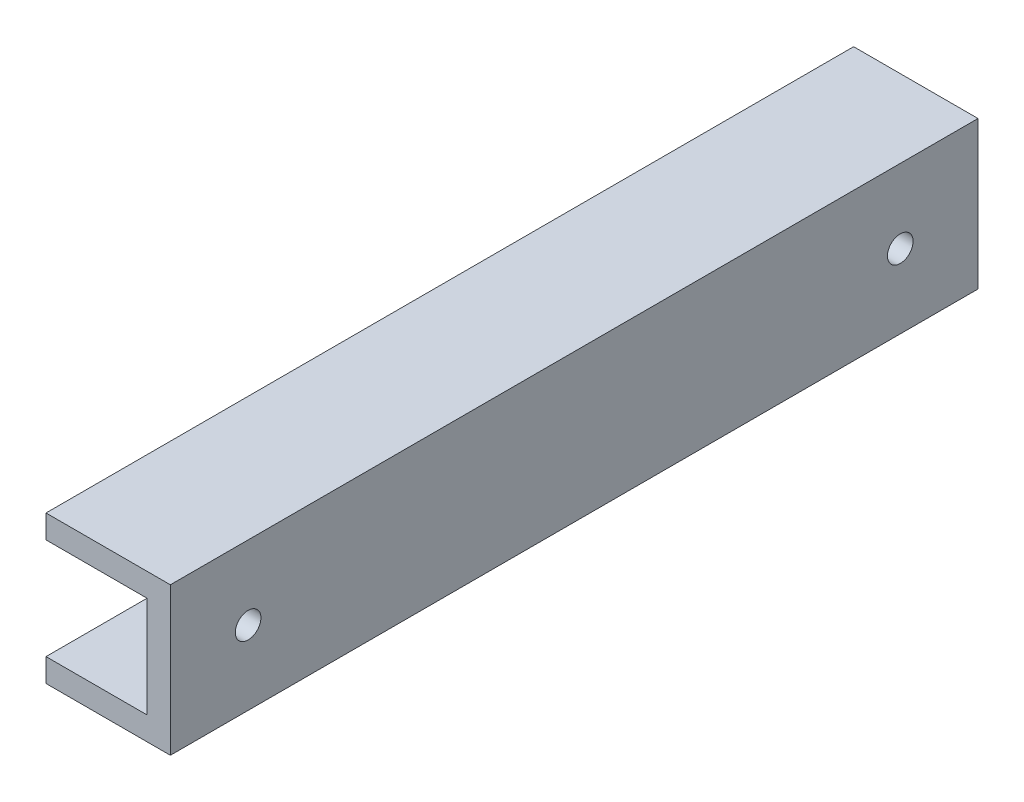
SolidWorks part; units mm, degrees
ref_plane "前视基准面" through (0, 0, 0) normal (0, 0, 1) x (1, 0, 0)
ref_plane "上视基准面" through (0, 0, 0) normal (0, 1, 0) x (1, 0, 0)
ref_plane "右视基准面" through (0, 0, 0) normal (1, 0, 0) x (0, 0, -1)
sketch "草图1" plane through (0, 0, 0) normal (0, 0, 1) x (1, 0, 0)
  line L1 (0, 0) -> (13, 0)
  line L2 (0, 0) -> (0, 13)
  line L3 (0, 13) -> (13, 13)
  line L4 (13, 0) -> (13, 13)
  dimension "D1" = 13
  dimension "D2" = 13
extrude "拉伸-薄壁1" add sketch "草图1" along normal blind 103.9 thin thin type one direction wall 3
sketch "草图2" plane through (-3, 0, 0) normal (-1, 0, 0) x (0, 0, 1)
  line L0 (0, 16) -> (0, -3) construction
  line L1 (103.9, 16) -> (103.9, -3) construction
  circle A0 centre (10, 6.5) radius 1.65
  circle A1 centre (93.9, 6.5) radius 1.65
  dimension "D1" = 3.3
  dimension "D2" = 3.3
  dimension "D3" = 10
  dimension "D4" = 10
extrude "切除-拉伸1" cut sketch "草图2" against normal blind 30
sketch "草图3" plane through (-3, 0, 0) normal (-1, 0, 0) x (0, 0, 1)
  line L1 (-5.2954, 23.3125) -> (111.6198, 23.3125)
  line L2 (-5.2954, 23.3125) -> (-5.2954, -22.907)
  line L3 (-5.2954, -22.907) -> (111.6198, -22.907)
  line L4 (111.6198, 23.3125) -> (111.6198, -22.907)
extrude "切除-拉伸2" cut sketch "草图3" against normal blind 3
sketch "草图4" plane through (13, 0, 0) normal (-1, 0, 0) x (0, 0, 1)
  line L0 (103.9, 13) -> (0, 13) construction
  line L1 (23, 13) -> (28, 13)
  line L2 (23, 13) -> (23, 0)
  line L3 (23, 0) -> (28, 0)
  line L4 (28, 13) -> (28, 0)
  line L5 (103.9, 0) -> (0, 0) construction
  line L6 (103.9, 13) -> (0, 13) construction
  line L7 (75.9, 13) -> (80.9, 13)
  line L8 (75.9, 13) -> (75.9, 0)
  line L9 (75.9, 0) -> (80.9, 0)
  line L10 (80.9, 13) -> (80.9, 0)
  line L11 (103.9, 0) -> (0, 0) construction
  line L12 (103.9, 0) -> (103.9, 13) construction
  line L13 (0, 0) -> (0, 13) construction
  dimension "D1" = 23
  dimension "D2" = 23
  dimension "D3" = 5
  dimension "D4" = 5
extrude "凸台-拉伸1" add sketch "草图4" along normal blind 10
sketch "草图5" plane through (13, 0, 0) normal (-1, 0, 0) x (0, 0, 1)
  line L0 (28, 0) -> (28, 13) construction
  line L1 (28, 9) -> (75.9, 9)
  line L2 (28, 9) -> (28, 4)
  line L3 (28, 4) -> (75.9, 4)
  line L4 (75.9, 9) -> (75.9, 4)
  line L5 (75.9, 13) -> (75.9, 0) construction
  line L6 (75.9, 0) -> (28, 0) construction
  dimension "D1" = 5
  dimension "D2" = 4
extrude "凸台-拉伸2" add sketch "草图5" along normal blind 10
sketch "草图6" plane through (13, 0, 0) normal (-1, 0, 0) x (0, 0, 1)
  line L1 (23, 13) -> (80.9, 13)
  line L2 (23, 13) -> (23, 0)
  line L3 (23, 0) -> (80.9, 0)
  line L4 (80.9, 13) -> (80.9, 0)
extrude "凸台-拉伸3" add sketch "草图6" along normal blind 10
sketch "草图7" plane through (3, 0, 0) normal (-1, 0, 0) x (0, 0, 1)
  line L0 (23, 13) -> (23, 0) construction
  line L1 (23, 9) -> (80.9, 9)
  line L2 (23, 9) -> (23, 4)
  line L3 (23, 4) -> (80.9, 4)
  line L4 (80.9, 9) -> (80.9, 4)
  line L5 (80.9, 0) -> (80.9, 13) construction
  line L6 (103.9, 13) -> (0, 13) construction
  dimension "D1" = 5
  dimension "D2" = 4
extrude "凸台-拉伸4" [suppressed] add sketch "草图7" along normal blind 3
sketch "草图8" plane through (3, 0, 0) normal (-1, 0, 0) x (0, 0, 1)
  line L0 (23, 13) -> (23, 0) construction
  line L1 (23, 9) -> (80.9, 9)
  line L2 (23, 9) -> (23, 4)
  line L3 (23, 4) -> (80.9, 4)
  line L4 (80.9, 9) -> (80.9, 4)
  line L5 (80.9, 0) -> (80.9, 13) construction
  line L6 (103.9, 13) -> (0, 13) construction
  dimension "D1" = 5
  dimension "D2" = 4
extrude "切除-拉伸3" cut sketch "草图8" against normal blind 3
chamfer "倒角1" distance 3 angle 45 2 edges at (6, 6.5, 80.9) (6, 6.5, 23)
chamfer "倒角2" distance 4 angle 45 2 edges at (13, 6.5, 80.9) (13, 6.5, 23)
